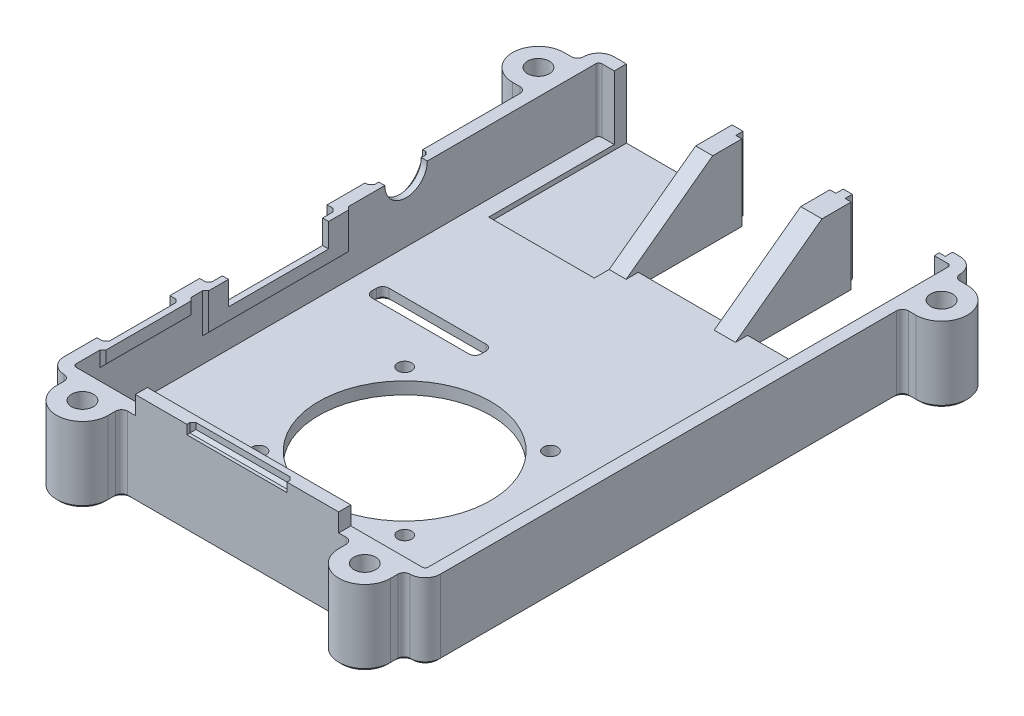
SolidWorks part; units mm, degrees
ref_plane "Front Plane" through (0, 0, 0) normal (0, 0, 1) x (1, 0, 0)
ref_plane "Top Plane" through (0, 0, 0) normal (0, 1, 0) x (1, 0, 0)
ref_plane "Right Plane" through (0, 0, 0) normal (1, 0, 0) x (0, 0, -1)
sketch "Sketch2" plane through (0, 0, 0) normal (0, 1, 0) x (1, 0, 0)
  line L1 (2.5, 0) -> (59.5, 0)
  line L2 (0, 2.5) -> (0, 88.1)
  line L3 (2.5, 90.6) -> (59.5, 90.6)
  line L4 (62, 2.5) -> (62, 88.1)
  arc A0 (0, 2.5) -> (2.5, 0) centre (2.5, 2.5) ccw
  arc A1 (59.5, 0) -> (62, 2.5) centre (59.5, 2.5) ccw
  arc A2 (62, 88.1) -> (59.5, 90.6) centre (59.5, 88.1) ccw
  arc A3 (2.5, 90.6) -> (0, 88.1) centre (2.5, 88.1) ccw
  point P7 (0, 0)
  point P10 (62, 0)
  point P13 (62, 90.6)
  point P16 (0, 90.6)
  dimension "D3" = 2.5
  dimension "D1" = 62
  dimension "D2" = 90.6
extrude "Base" add sketch "Sketch2" along normal blind 12.5
shell "Shell" thickness 2 removed face at (31, 12.5, -45.3)
sketch "Sketch14" plane through (0, 0, 0) normal (0, -1, 0) x (1, 0, 0)
  line L0 (31, 0) -> (31, -90.6) construction
  line L2 (59.5, -90.6) -> (2.5, -90.6) construction
  line L3 (-2.2, -78.6) -> (0, -78.6)
  line L4 (0, -88.1) -> (0, -2.5) construction
  line L5 (0, -78.6) -> (0, -87.1)
  line L6 (0, -87.1) -> (-2.2, -87.1)
  line L7 (3.5, 2.2) -> (3.5, 0)
  line L8 (2.5, 0) -> (59.5, 0) construction
  line L9 (3.5, 0) -> (12, 0)
  line L10 (12, 0) -> (12, 2.2)
  line L11 (64.2, -78.6) -> (62, -78.6)
  line L12 (62, -87.1) -> (64.2, -87.1)
  line L13 (62, -78.6) -> (62, -87.1)
  line L14 (50, 0) -> (50, 2.2)
  line L15 (58.5, 0) -> (50, 0)
  line L16 (58.5, 2.2) -> (58.5, 0)
  line L17 (2.5, 0) -> (59.5, 0) construction
  arc A0 (-2.2, -78.6) -> (-2.2, -87.1) centre (-2.2, -82.85) ccw
  arc A1 (3.5, 2.2) -> (12, 2.2) centre (7.75, 2.2) cw
  arc A2 (64.2, -78.6) -> (64.2, -87.1) centre (64.2, -82.85) cw
  arc A3 (58.5, 2.2) -> (50, 2.2) centre (54.25, 2.2) ccw
  dimension "D1" = 2.2
  dimension "D2" = 8.5
  dimension "D3" = 3.5
  dimension "D4" = 3.5
extrude "Clamps" add sketch "Sketch14" against normal up to surface (12.5 mm away) up to face at (31, 12.5, -45.3)
fillet "Clamp Fillets" radius 1 8 edges at (50, 6.25, 0) (58.5, 6.25, 0) (12, 6.25, 0) (3.5, 6.25, 0) (0, 6.25, -87.1) (0, 6.25, -78.6) (62, 6.25, -78.6) (62, 6.25, -87.1)
sketch "Sketch20" plane through (0, 0, 0) normal (0, -1, 0) x (1, 0, 0)
  circle A0 centre (7.75, 2.2) radius 1.8
  circle A1 centre (54.25, 2.2) radius 1.8
  circle A2 centre (64.2, -82.85) radius 1.8
  circle A3 centre (-2.2, -82.85) radius 1.8
  arc A4 (12, 2.2) -> (3.5, 2.2) centre (7.75, 2.2) ccw construction
  arc A5 (58.5, 2.2) -> (50, 2.2) centre (54.25, 2.2) ccw construction
  arc A6 (-2.2, -78.6) -> (-2.2, -87.1) centre (-2.2, -82.85) ccw construction
  arc A7 (64.2, -87.1) -> (64.2, -78.6) centre (64.2, -82.85) ccw construction
  dimension "D1" = 3.6
extrude "Clamp Holes" cut sketch "Sketch20" against normal through all
sketch "Sketch21" plane through (0, 0, 0) normal (0, -1, 0) x (1, 0, 0)
  circle A0 centre (7.75, 2.2) radius 2.9
  circle A1 centre (54.25, 2.2) radius 2.9
  circle A2 centre (64.2, -82.85) radius 2.9
  circle A3 centre (-2.2, -82.85) radius 2.9
  circle A4 centre (-2.2, -82.85) radius 1.8 construction
  circle A5 centre (7.75, 2.2) radius 1.8 construction
  circle A6 centre (54.25, 2.2) radius 1.8 construction
  circle A7 centre (64.2, -82.85) radius 1.8 construction
  dimension "D1" = 5.8
extrude "Clamp Countersinks" cut sketch "Sketch21" against normal blind 3.4
chamfer "Clamp Countersink Chamfers" distance 0.3 angle 45 4 edges at (-2.2, 0, -85.75) (64.2, 0, -85.75) (54.25, 0, -0.7) (7.75, 0, -0.7)
sketch "Sketch22" plane through (0, 12.5, 0) normal (0, 1, 0) x (1, 0, 0)
  line L0 (31, 2) -> (31, 0) construction
  line L1 (2.5, 2) -> (59.5, 2) construction
  line L2 (13, 0) -> (49, 0) construction
  line L4 (14.25, 2) -> (47.75, 2)
  line L5 (14.25, 2) -> (14.25, 0)
  line L6 (14.25, 0) -> (47.75, 0)
  line L7 (47.75, 2) -> (47.75, 0)
  dimension "D1" = 16.75
  dimension "D2" = 33.5
extrude "SD Fill" add sketch "Sketch22" along normal blind 3
sketch "Sketch23" plane through (0, 0, 0) normal (0, 0, 1) x (1, 0, 0)
  line L0 (31, 15.5) -> (31, 0) construction
  line L1 (14.25, 15.5) -> (47.75, 15.5) construction
  line L2 (13, 0) -> (49, 0) construction
  line L4 (22.75, 15.5) -> (39.25, 15.5)
  line L5 (22.75, 15.5) -> (22.75, 14)
  line L6 (22.75, 14) -> (39.25, 14)
  line L7 (39.25, 15.5) -> (39.25, 14)
  dimension "D1" = 8.25
  dimension "D2" = 16.5
  dimension "D3" = 1.5
extrude "SD Approach" cut sketch "Sketch23" against normal blind 1
chamfer "SD Approach Chamfer" distance 0.5 angle 45 3 edges at (39.25, 14.75, -1) (31, 14, -1) (22.75, 14.75, -1)
sketch "Sketch24" plane through (0, 0, -90.6) normal (0, 0, -1) x (-1, 0, 0)
  line L0 (-59.5, 12.5) -> (-2.5, 12.5) construction
  line L1 (-57.25, 12.5) -> (-42.75, 12.5)
  line L2 (-57.25, 12.5) -> (-57.25, 0)
  line L3 (-57.25, 0) -> (-42.75, 0)
  line L4 (-42.75, 12.5) -> (-42.75, 0)
  line L5 (-59.5, 0) -> (-2.5, 0) construction
  line L6 (0, 12.5) -> (0, 0) construction
  line L7 (-39.25, 12.5) -> (-24.75, 12.5)
  line L8 (-39.25, 12.5) -> (-39.25, 0)
  line L9 (-39.25, 0) -> (-24.75, 0)
  line L10 (-24.75, 12.5) -> (-24.75, 0)
  dimension "D1" = 14.5
  dimension "D2" = 24.75
  dimension "D3" = 42.75
extrude "USB Cutout" cut sketch "Sketch24" against normal blind 18.25
sketch "Sketch25" plane through (0, 0, -90.6) normal (0, 0, -1) x (-1, 0, 0)
  line L0 (-42.75, 12.5) -> (-39.25, 12.5) construction
  line L1 (-41.75, 12.5) -> (-58.25, 12.5)
  line L2 (-41.75, 12.5) -> (-41.75, 0)
  line L3 (-41.75, 0) -> (-58.25, 0)
  line L4 (-58.25, 12.5) -> (-58.25, 0)
  line L5 (-59.5, 0) -> (-57.25, 0) construction
  line L6 (-24.75, 12.5) -> (-2.5, 12.5) construction
  line L7 (-23.75, 12.5) -> (-40.25, 12.5)
  line L8 (-23.75, 12.5) -> (-23.75, 0)
  line L9 (-23.75, 0) -> (-40.25, 0)
  line L10 (-40.25, 12.5) -> (-40.25, 0)
  line L11 (-42.75, 0) -> (-39.25, 0) construction
  line L12 (-57.25, 12.5) -> (-57.25, 0) construction
  line L13 (-42.75, 0) -> (-42.75, 12.5) construction
  line L14 (-39.25, 12.5) -> (-39.25, 0) construction
  line L15 (-24.75, 0) -> (-24.75, 12.5) construction
  point P18 (-57.25, 6.25)
  dimension "D1" = 1
  dimension "D2" = 1
  dimension "D3" = 1
  dimension "D4" = 1
extrude "USB Approach" cut sketch "Sketch25" against normal blind 1.2
sketch "Sketch26" plane through (42.75, 0, 0) normal (1, 0, 0) x (0, 0, -1)
  line L0 (88.6, 2) -> (88.6, 12.5)
  line L1 (88.6, 12.5) -> (84.6, 12.5)
  line L2 (88.6, 2) -> (70.35, 2)
  line L3 (70.35, 2) -> (84.6, 12.5)
  line L4 (90.6, 0) -> (90.6, 12.5) construction
  line L5 (72.35, 0) -> (72.35, 2) construction
  dimension "D1" = 6
  dimension "D2" = 2
extrude "USB Inner Support" add sketch "Sketch26" against normal up to surface (3.5 mm away) up to face at (39.25, 4.8333, -83.45)
sketch "Sketch27" plane through (24.75, 0, 0) normal (1, 0, 0) x (0, 0, -1)
  line L0 (88.6, 2) -> (88.6, 12.5)
  line L1 (88.6, 12.5) -> (84.6, 12.5)
  line L2 (88.6, 2) -> (70.35, 2)
  line L3 (70.35, 2) -> (84.6, 12.5)
  line L4 (90.6, 0) -> (90.6, 12.5) construction
  line L5 (72.35, 0) -> (72.35, 2) construction
  dimension "D1" = 6
  dimension "D2" = 2
extrude "USB Outer Support" add sketch "Sketch27" against normal blind 2.8
sketch "Sketch28" plane through (0, 0, -90.6) normal (0, 0, -1) x (-1, 0, 0)
  line L0 (-23.75, 12.5) -> (-2.5, 12.5) construction
  line L1 (-21.95, 12.5) -> (-4.55, 12.5)
  line L2 (-21.95, 12.5) -> (-21.95, 1.2)
  line L3 (-21.95, 1.2) -> (-4.55, 1.2)
  line L4 (-4.55, 12.5) -> (-4.55, 1.2)
  line L5 (0, 12.5) -> (0, 0) construction
  dimension "D1" = 17.4
  dimension "D2" = 4.55
  dimension "D3" = 11.3
extrude "RJ45 Cutout" cut sketch "Sketch28" against normal blind 22.7
sketch "Sketch29" plane through (2, 0, 0) normal (1, 0, 0) x (0, 0, -1)
  line L0 (88.1, 12.5) -> (2.5, 12.5) construction
  line L1 (6.45, 12.5) -> (21.45, 12.5)
  line L2 (6.45, 12.5) -> (6.45, 10)
  line L3 (6.45, 10) -> (21.45, 10)
  line L4 (21.45, 12.5) -> (21.45, 10)
  line L5 (0, 12.5) -> (0, 0) construction
  line L6 (23.35, 12.5) -> (47.35, 12.5)
  line L7 (23.35, 12.5) -> (23.35, 6.07)
  line L8 (23.35, 6.07) -> (47.35, 6.07)
  line L9 (47.35, 12.5) -> (47.35, 6.07)
  dimension "D1" = 24
  dimension "D2" = 15
  dimension "D3" = 6.45
  dimension "D4" = 23.35
  dimension "D5" = 2.5
  dimension "D6" = 6.43
extrude "HDMI Support" add sketch "Sketch29" along normal blind 0.5
chamfer "HDMI Support Chamfer" distance 0.5 angle 45 6 edges at (2.5, 9.285, -47.35) (2.5, 6.07, -35.35) (2.5, 9.285, -23.35) (2.5, 11.25, -21.45) (2.5, 10, -13.95) (2.5, 11.25, -6.45)
sketch "Sketch30" plane through (0, 0, 0) normal (-1, 0, 0) x (0, 0, 1)
  line L0 (-77.6, 12.5) -> (-2.5, 12.5) construction
  line L1 (-24.85, 12.5) -> (-45.85, 12.5)
  line L2 (-24.85, 12.5) -> (-24.85, 6.57)
  line L3 (-24.85, 6.57) -> (-45.85, 6.57)
  line L4 (-45.85, 12.5) -> (-45.85, 6.57)
  line L5 (0, 12.5) -> (0, 0) construction
  line L6 (-19.95, 12.5) -> (-7.95, 12.5)
  line L7 (-19.95, 12.5) -> (-19.95, 10.5)
  line L8 (-19.95, 10.5) -> (-7.95, 10.5)
  line L9 (-7.95, 12.5) -> (-7.95, 10.5)
  dimension "D1" = 12
  dimension "D2" = 21
  dimension "D3" = 7.95
  dimension "D4" = 24.85
  dimension "D5" = 5.93
  dimension "D6" = 2
extrude "HDMI Approach" cut sketch "Sketch30" against normal blind 1.5
sketch "Sketch31" plane through (1.5, 0, 0) normal (-1, 0, 0) x (0, 0, 1)
  line L0 (-24.85, 12.5) -> (-45.85, 12.5) construction
  line L1 (-43.6, 12.5) -> (-27.1, 12.5)
  line L2 (-43.6, 12.5) -> (-43.6, 8.57)
  line L3 (-43.6, 8.57) -> (-27.1, 8.57)
  line L4 (-27.1, 12.5) -> (-27.1, 8.57)
  line L5 (-45.85, 12.5) -> (-45.85, 6.57) construction
  line L6 (-24.85, 6.57) -> (-24.85, 12.5) construction
  line L7 (-45.85, 6.57) -> (-24.85, 6.57) construction
  dimension "D1" = 2.25
  dimension "D2" = 2.25
  dimension "D3" = 2
extrude "HDMI Cutout" cut sketch "Sketch31" against normal blind 1
chamfer "HDMI Approach Chamfer" distance 0.5 angle 45 6 edges at (1.5, 11.5, -7.95) (1.5, 10.5, -13.95) (1.5, 11.5, -19.95) (1.5, 9.535, -24.85) (1.5, 6.57, -35.35) (1.5, 9.535, -45.85)
sketch "Sketch32" plane through (0, 0, 0) normal (-1, 0, 0) x (0, 0, 1)
  line L0 (-77.6, 12.5) -> (-45.85, 12.5) construction
  line L1 (0, 12.5) -> (0, 0) construction
  circle A0 centre (-56.85, 12.5) radius 3.5
  dimension "D1" = 7
  dimension "D2" = 56.85
extrude "Audio Cutout" cut sketch "Sketch32" against normal blind 2
sketch "Sketch33" plane through (0, 0, 0) normal (-1, 0, 0) x (0, 0, 1)
  circle A0 centre (-56.85, 12.5) radius 4.75
  arc A1 (-60.35, 12.5) -> (-53.35, 12.5) centre (-56.85, 12.5) ccw construction
  dimension "D1" = 9.5
extrude "Audio Approach" cut sketch "Sketch33" against normal blind 1
chamfer "Audio Approach Chamfer" distance 0.5 angle 45 1 edges at (1, 7.75, -56.85)
sketch "Sketch34" plane through (0, 0, 0) normal (0, -1, 0) x (1, 0, 0)
  line L0 (62, -2.5) -> (62, -77.6) construction
  line L1 (52.5, -9.4) -> (58.5, -9.4)
  line L2 (52.5, -9.4) -> (52.5, -62.1)
  line L3 (52.5, -62.1) -> (58.5, -62.1)
  line L4 (58.5, -9.4) -> (58.5, -62.1)
  line L5 (13, 0) -> (49, 0) construction
  point P6 (55.5, -9.4)
  dimension "D1" = 6
  dimension "D2" = 52.7
  dimension "D3" = 3.5
  dimension "D4" = 9.4
extrude "Header Cutout" cut sketch "Sketch34" against normal blind 2
sketch "Sketch35" plane through (0, 0, 0) normal (0, -1, 0) x (1, 0, 0)
  line L0 (55.5, -9.4) -> (55.5, -62.1) construction
  line L1 (58.5, -9.4) -> (52.5, -9.4) construction
  line L2 (52.5, -62.1) -> (58.5, -62.1) construction
  line L3 (52.5, -35.75) -> (58.5, -35.75) construction
  line L4 (52.5, -9.4) -> (52.5, -62.1) construction
  line L5 (58.5, -62.1) -> (58.5, -9.4) construction
  line L6 (56, -9.4) -> (55, -9.4)
  line L7 (55, -9.4) -> (55, -10.4)
  line L8 (55, -10.4) -> (53.5, -10.4)
  line L9 (53.5, -10.4) -> (53.5, -15.3625)
  line L10 (53.5, -15.3625) -> (52.5, -15.3625)
  line L11 (52.5, -15.3625) -> (52.5, -16.3625)
  line L12 (52.5, -16.3625) -> (53.5, -16.3625)
  line L13 (53.5, -16.3625) -> (53.5, -28.2875)
  line L14 (53.5, -28.2875) -> (52.5, -28.2875)
  line L15 (52.5, -28.2875) -> (52.5, -29.2875)
  line L16 (52.5, -29.2875) -> (53.5, -29.2875)
  line L17 (53.5, -29.2875) -> (53.5, -34.25)
  line L18 (53.5, -34.25) -> (55, -34.25)
  line L19 (55, -34.25) -> (55, -35.25)
  line L20 (55, -35.25) -> (52.5, -35.25)
  line L21 (52.5, -35.25) -> (52.5, -36.25)
  line L22 (56, -62.1) -> (55, -62.1)
  line L23 (55, -36.25) -> (52.5, -36.25)
  line L24 (55, -37.25) -> (55, -36.25)
  line L25 (53.5, -37.25) -> (55, -37.25)
  line L26 (53.5, -42.2125) -> (53.5, -37.25)
  line L27 (52.5, -42.2125) -> (53.5, -42.2125)
  line L28 (52.5, -43.2125) -> (52.5, -42.2125)
  line L29 (53.5, -43.2125) -> (52.5, -43.2125)
  line L30 (53.5, -55.1375) -> (53.5, -43.2125)
  line L31 (52.5, -55.1375) -> (53.5, -55.1375)
  line L32 (52.5, -56.1375) -> (52.5, -55.1375)
  line L33 (53.5, -56.1375) -> (52.5, -56.1375)
  line L34 (53.5, -61.1) -> (53.5, -56.1375)
  line L35 (55, -61.1) -> (53.5, -61.1)
  line L36 (55, -62.1) -> (55, -61.1)
  line L37 (56, -62.1) -> (56, -61.1)
  line L38 (56, -61.1) -> (57.5, -61.1)
  line L39 (57.5, -61.1) -> (57.5, -56.1375)
  line L40 (57.5, -56.1375) -> (58.5, -56.1375)
  line L41 (58.5, -56.1375) -> (58.5, -55.1375)
  line L42 (58.5, -55.1375) -> (57.5, -55.1375)
  line L43 (57.5, -55.1375) -> (57.5, -43.2125)
  line L44 (57.5, -43.2125) -> (58.5, -43.2125)
  line L45 (58.5, -43.2125) -> (58.5, -42.2125)
  line L46 (58.5, -42.2125) -> (57.5, -42.2125)
  line L47 (57.5, -42.2125) -> (57.5, -37.25)
  line L48 (57.5, -37.25) -> (56, -37.25)
  line L49 (56, -37.25) -> (56, -36.25)
  line L50 (56, -36.25) -> (58.5, -36.25)
  line L51 (58.5, -35.25) -> (58.5, -36.25)
  line L52 (56, -35.25) -> (58.5, -35.25)
  line L53 (56, -34.25) -> (56, -35.25)
  line L54 (57.5, -34.25) -> (56, -34.25)
  line L55 (57.5, -29.2875) -> (57.5, -34.25)
  line L56 (58.5, -29.2875) -> (57.5, -29.2875)
  line L57 (58.5, -28.2875) -> (58.5, -29.2875)
  line L58 (57.5, -28.2875) -> (58.5, -28.2875)
  line L59 (57.5, -16.3625) -> (57.5, -28.2875)
  line L60 (58.5, -16.3625) -> (57.5, -16.3625)
  line L61 (58.5, -15.3625) -> (58.5, -16.3625)
  line L62 (57.5, -15.3625) -> (58.5, -15.3625)
  line L63 (57.5, -10.4) -> (57.5, -15.3625)
  line L64 (56, -10.4) -> (57.5, -10.4)
  line L65 (56, -9.4) -> (56, -10.4)
  dimension "D1" = 0.5
  dimension "D2" = 1
  dimension "D3" = 1.5
  dimension "D4" = 11.925
extrude "Header Cover" add sketch "Sketch35" against normal blind 1
chamfer "Shell Chamfer" distance 0.5 angle 45 46 edges at (53.75, 0, -62.1) (52.5, 0, -59.1188) (52.5, 0, -49.175) (52.5, 0, -39.2312) (52.5, 0, -32.2687) (52.5, 0, -22.325) (52.5, 0, -12.3812) (53.75, 0, -9.4) (57.25, 0, -9.4) (58.5, 0, -12.3812) (58.5, 0, -22.325) (58.5, 0, -32.2687) (58.5, 0, -39.2312) (58.5, 0, -49.175) (58.5, 0, -59.1187) (57.25, 0, -62.1) (41, 0, -90.6) (58.875, 0, -90.6) (61.2678, 0, -89.8678) (62.2929, 0, -87.3929) (63.6, 0, -87.1) (68.45, 0, -82.85) (63.6, 0, -78.6) (62.2929, 0, -78.3071) (62, 0, -40.05) (13.125, 0, -90.6) (0.7322, 0, -89.8678) (-0.2929, 0, -87.3929) (-1.6, 0, -87.1) (-6.45, 0, -82.85) (-1.6, 0, -78.6) (0, 0, -40.05) (61.2678, 0, -0.7322) (58.7929, 0, 0.2929) (58.5, 0, 1.6) (54.25, 0, 6.45) (50, 0, 1.6) (49.7071, 0, 0.2929) (0.7322, 0, -0.7322) (3.5, 0, 1.6) (7.75, 0, 6.45) (12, 0, 1.6) (12.2929, 0, 0.2929) (31, 0, 0) (-0.2929, 0, -78.3071) (3.2071, 0, 0.2929)
sketch "Sketch38" plane through (0, 0, 0) normal (0, -1, 0) x (1, 0, 0)
  line L0 (31, 0) -> (31, -72.35) construction
  line L1 (13, 0) -> (49, 0) construction
  line L2 (39.25, -72.35) -> (24.75, -72.35) construction
  line L3 (31, -27.63) -> (43, -15.63) construction
  line L4 (31, -27.63) -> (43, -39.63) construction
  circle A0 centre (31, -27.63) radius 14.15
  circle A1 centre (31, -27.63) radius 16.9706 construction
  circle A2 centre (43, -15.63) radius 1.15
  circle A3 centre (43, -39.63) radius 1.15
  circle A4 centre (19, -15.63) radius 1.15
  circle A5 centre (19, -39.63) radius 1.15
  dimension "D1" = 28.3
  dimension "D2" = 33.9412
  dimension "D3" = 27.63
  dimension "D6" = 2.3
  dimension "D4" = 45
  dimension "D5" = 45
sketch "Sketch36" plane through (0, 0, 0) normal (0, -1, 0) x (1, 0, 0)
  line L0 (13, 0) -> (49, 0) construction
  line L1 (23.1, -5.7) -> (39.1, -5.7)
  line L2 (22.1, -6.7) -> (22.1, -7.5)
  line L3 (23.1, -8.5) -> (39.1, -8.5)
  line L4 (40.1, -6.7) -> (40.1, -7.5)
  line L5 (0, -77.6) -> (0, -2.5) construction
  line L7 (6.45, -46.76) -> (22.45, -46.76)
  line L8 (5.45, -47.76) -> (5.45, -48.56)
  line L9 (6.45, -49.56) -> (22.45, -49.56)
  line L10 (23.45, -47.76) -> (23.45, -48.56)
  arc A0 (22.1, -7.5) -> (23.1, -8.5) centre (23.1, -7.5) ccw
  arc A1 (39.1, -8.5) -> (40.1, -7.5) centre (39.1, -7.5) ccw
  arc A2 (40.1, -6.7) -> (39.1, -5.7) centre (39.1, -6.7) ccw
  arc A3 (23.1, -5.7) -> (22.1, -6.7) centre (23.1, -6.7) ccw
  arc A4 (5.45, -48.56) -> (6.45, -49.56) centre (6.45, -48.56) ccw
  arc A5 (23.45, -48.56) -> (22.45, -49.56) centre (22.45, -48.56) cw
  arc A6 (23.45, -47.76) -> (22.45, -46.76) centre (22.45, -47.76) ccw
  arc A7 (6.45, -46.76) -> (5.45, -47.76) centre (6.45, -47.76) ccw
  point P14 (40.1, -5.7)
  point P17 (22.1, -5.7)
  point P25 (5.45, -49.56)
  point P28 (23.45, -49.56)
  point P31 (23.45, -46.76)
  dimension "D5" = 46.76
  dimension "D8" = 1
  dimension "D1" = 5.7
  dimension "D2" = 22.1
  dimension "D3" = 2.8
  dimension "D4" = 18
  dimension "D6" = 18
  dimension "D7" = 2.8
  dimension "D9" = 5.45
extrude "Ribbon Slots" cut sketch "Sketch36" against normal blind 2
extrude "Fan Mount" cut sketch "Sketch38" against normal blind 2
chamfer "Ribbon Chamfers" distance 0.5 angle 45 16 edges at (22.3929, 0, -8.2071) (22.1, 0, -7.1) (22.3929, 0, -5.9929) (31.1, 0, -5.7) (31.1, 0, -8.5) (39.8071, 0, -8.2071) (39.8071, 0, -5.9929) (40.1, 0, -7.1) (23.1571, 0, -47.0529) (23.45, 0, -48.16) (23.1571, 0, -49.2671) (14.45, 0, -49.56) (5.7429, 0, -49.2671) (14.45, 0, -46.76) (5.7429, 0, -47.0529) (5.45, 0, -48.16)
